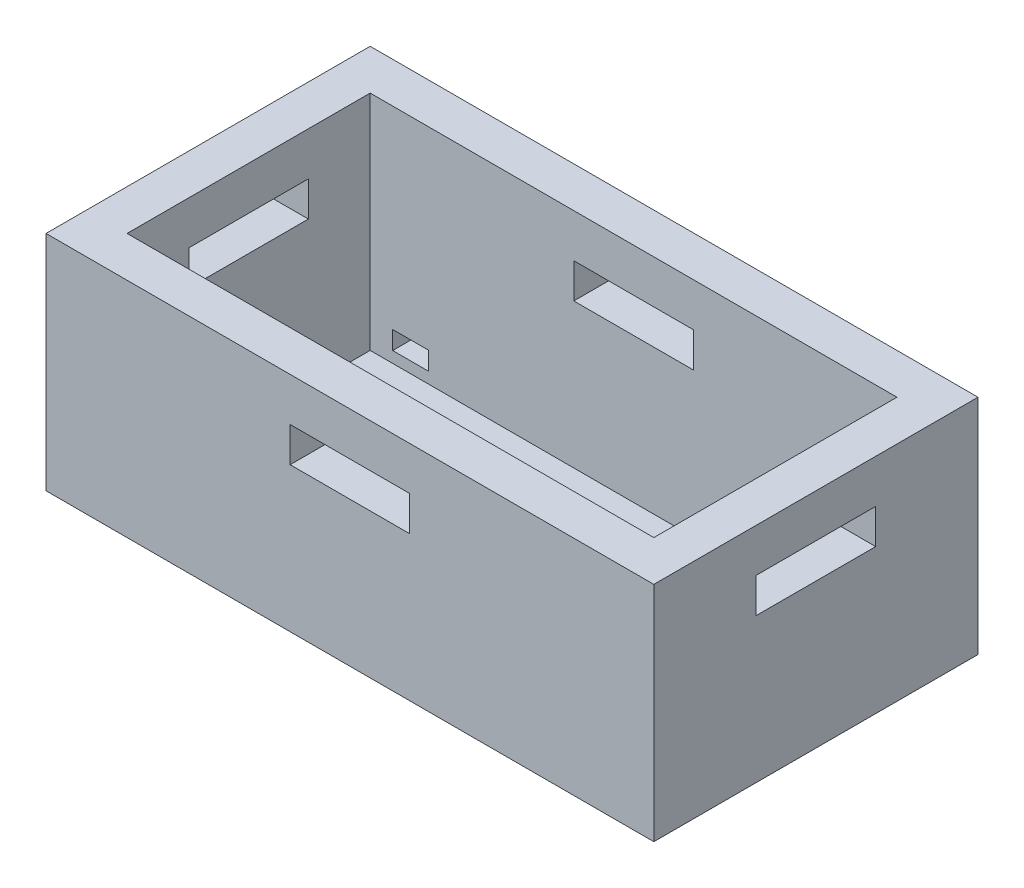
SolidWorks part; units mm, degrees
ref_plane "Alzado" through (0, 0, 0) normal (0, 0, 1) x (1, 0, 0)
ref_plane "Planta" through (0, 0, 0) normal (0, 1, 0) x (1, 0, 0)
ref_plane "Vista lateral" through (0, 0, 0) normal (1, 0, 0) x (0, 0, -1)
sketch "Croquis1" plane through (0, 0, 0) normal (0, 1, 0) x (1, 0, 0)
  line L1 (65, -30) -> (-65, -30)
  line L2 (65, -30) -> (65, 30)
  line L3 (65, 30) -> (-65, 30)
  line L4 (-65, -30) -> (-65, 30)
  line L5 (65, -30) -> (-65, 30) construction
  line L6 (65, 30) -> (-65, -30) construction
  line L7 (75, -40) -> (-75, -40)
  line L8 (75, -40) -> (75, 40)
  line L9 (75, 40) -> (-75, 40)
  line L10 (-75, -40) -> (-75, 40)
  line L11 (75, -40) -> (-75, 40) construction
  line L12 (75, 40) -> (-75, -40) construction
  point P0 (0, 0)
  point P6 (0, 0)
  dimension "D1" = 130
  dimension "D2" = 60
  dimension "D3" = 10
  dimension "D4" = 10
extrude "Saliente-Extruir1" add sketch "Croquis1" against normal blind 7.5 contours L4 L1 L2 L3 region at (0, 0, 0)
extrude "Saliente-Extruir2" add sketch "Croquis1<3>" along normal blind 55 separate body
sketch "Croquis1<3>" plane through (0, 0, 0) normal (0, 1, 0) x (1, 0, 0) same geometry as "Croquis1"
sketch "Croquis2" plane through (0, 0, 0) normal (0, 1, 0) x (1, 0, 0)
  line L0 (-75, 0) -> (75, 0) construction
  line L1 (-75, 40) -> (-75, -40) construction
  line L2 (75, -40) -> (75, 40) construction
  line L3 (0, 40) -> (0, -40) construction
  line L4 (75, 40) -> (-75, 40) construction
  line L5 (-75, -40) -> (75, -40) construction
  line L6 (58, 4) -> (65, 4)
  line L7 (-58, -4) -> (-65, -4)
  line L8 (-58, -4) -> (-58, 4)
  line L9 (-58, 4) -> (-65, 4)
  line L10 (-65, -4) -> (-65, 4)
  line L11 (-58, -4) -> (-65, 4) construction
  line L12 (-58, 4) -> (-65, -4) construction
  line L13 (58, -4) -> (65, 4) construction
  line L14 (58, 4) -> (65, -4) construction
  line L15 (58, -4) -> (65, -4)
  line L16 (65, -4) -> (65, 4)
  line L17 (58, -4) -> (58, 4)
  line L18 (-65, 30) -> (-65, -30) construction
  point P12 (-61.5, 0)
  dimension "D1" = 8
  dimension "D2" = 7
extrude "Cortar-Extruir1" cut sketch "Croquis2" against normal through all
sketch "Croquis3" plane through (0, 0, 40) normal (0, 0, 1) x (1, 0, 0)
  line L0 (0, 0) -> (0, 55) construction
  line L1 (-75, 0) -> (75, 0) construction
  line L2 (-75, 55) -> (75, 55) construction
  line L4 (14.75, 44.3) -> (-14.75, 44.3)
  line L5 (14.75, 44.3) -> (14.75, 35.7)
  line L6 (14.75, 35.7) -> (-14.75, 35.7)
  line L7 (-14.75, 44.3) -> (-14.75, 35.7)
  line L8 (14.75, 44.3) -> (-14.75, 35.7) construction
  line L9 (14.75, 35.7) -> (-14.75, 44.3) construction
  point P6 (0, 40)
  dimension "D1" = 29.5
  dimension "D2" = 8.6
  dimension "D3" = 40
extrude "Cortar-Extruir2" cut sketch "Croquis3" against normal through all
sketch "Croquis4" plane through (0, 0, -40) normal (0, 0, -1) x (-1, 0, 0)
  line L0 (-75, 5) -> (75, 5) construction
  line L1 (-75, 55) -> (-75, 0) construction
  line L2 (75, 55) -> (75, 0) construction
  line L3 (-75, 0) -> (75, 0) construction
  line L4 (0, 0) -> (0, 55) construction
  line L5 (-50.55, 2.75) -> (-59.45, 2.75)
  line L6 (-50.55, 2.75) -> (-50.55, 7.25)
  line L7 (-50.55, 7.25) -> (-59.45, 7.25)
  line L8 (-59.45, 2.75) -> (-59.45, 7.25)
  line L9 (-50.55, 2.75) -> (-59.45, 7.25) construction
  line L10 (-50.55, 7.25) -> (-59.45, 2.75) construction
  line L11 (-75, 55) -> (75, 55) construction
  line L12 (50.55, 2.75) -> (59.45, 2.75)
  line L13 (50.55, 2.75) -> (50.55, 7.25)
  line L14 (59.45, 2.75) -> (59.45, 7.25)
  line L15 (50.55, 7.25) -> (59.45, 7.25)
  point P8 (-55, 5)
  dimension "D1" = 5
  dimension "D2" = 8.9
  dimension "D3" = 4.5
  dimension "D4" = 20
extrude "Cortar-Extruir3" cut sketch "Croquis4" against normal up to next (10 mm away)
sketch "Croquis5" plane through (75, 0, 0) normal (1, 0, 0) x (0, 0, -1)
  line L0 (0, 55) -> (0, 0) construction
  line L1 (-40, 0) -> (40, 0) construction
  line L2 (-40, 55) -> (40, 55) construction
  line L4 (14.75, 44.3) -> (-14.75, 44.3)
  line L5 (14.75, 44.3) -> (14.75, 35.7)
  line L6 (14.75, 35.7) -> (-14.75, 35.7)
  line L7 (-14.75, 44.3) -> (-14.75, 35.7)
  line L8 (14.75, 44.3) -> (-14.75, 35.7) construction
  line L9 (14.75, 35.7) -> (-14.75, 44.3) construction
  point P7 (0, 40)
  dimension "D1" = 10.7
  dimension "D2" = 29.5
  dimension "D3" = 8.6
extrude "Cortar-Extruir4" cut sketch "Croquis5" against normal through all
